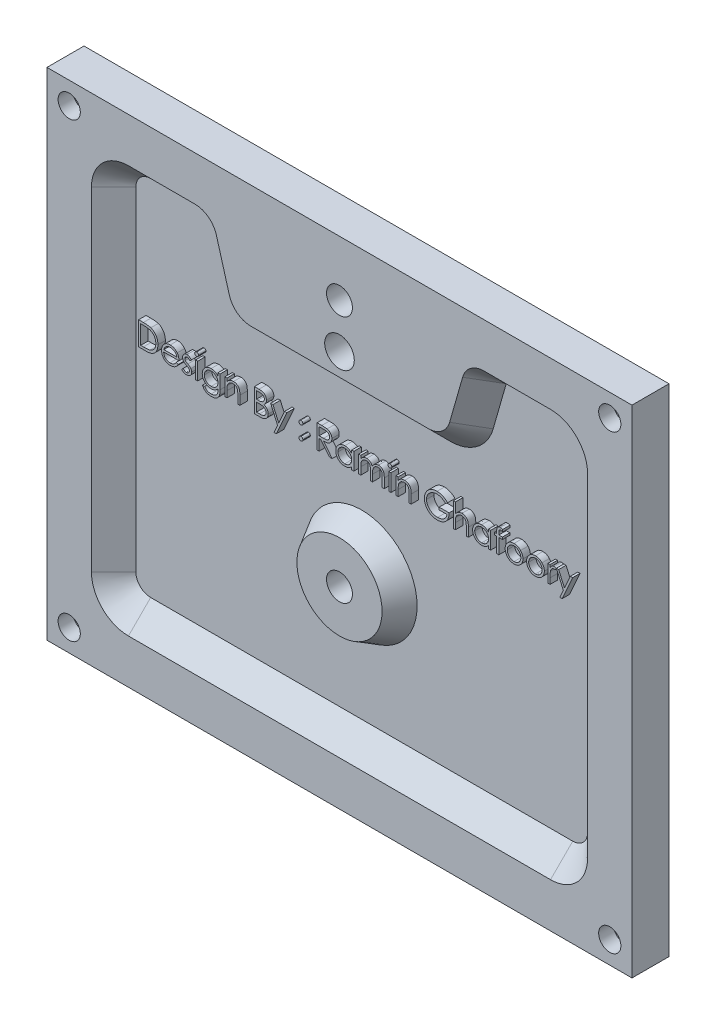
SolidWorks part; units mm, degrees
material "Ductile Iron"
ref_plane "Front" through (0, 0, 0) normal (0, 0, 1) x (1, 0, 0)
ref_plane "Top" through (0, 0, 0) normal (0, 1, 0) x (1, 0, 0)
ref_plane "Right" through (0, 0, 0) normal (1, 0, 0) x (0, 0, -1)
sketch "Sketch1" plane through (0, 0, 0) normal (0, 0, 1) x (1, 0, 0)
  line L1 (79, 67) -> (-79, 67)
  line L2 (79, 67) -> (79, -67)
  line L3 (79, -67) -> (-79, -67)
  line L4 (-79, 67) -> (-79, -67)
  point P4 (79, 0)
  point P6 (0, 67)
  dimension "D1" = 158
  dimension "D2" = 134
extrude "Boss-Extrude1" add sketch "Sketch1" along normal blind 10
sketch "Sketch2" plane through (0, 0, 10) normal (0, 0, 1) x (1, 0, 0)
  line L0 (-79, 67) -> (-79, -67) construction
  line L1 (57, 55) -> (39.0258, 55)
  line L2 (67, 45) -> (67, -45)
  line L3 (57, -55) -> (-57, -55)
  line L4 (-67, 45) -> (-67, -45)
  line L5 (79, 67) -> (-79, 67) construction
  line L6 (-79, -67) -> (79, -67) construction
  line L7 (79, -67) -> (79, 67) construction
  line L8 (33.2567, 50.6483) -> (29.7433, 38.3517)
  line L9 (23.9742, 34) -> (-23.9742, 34)
  line L10 (-29.7433, 38.3517) -> (-33.2567, 50.6483)
  line L11 (0, 0) -> (0, 34) construction
  line L12 (-39.0258, 55) -> (-57, 55)
  arc A0 (67, 45) -> (57, 55) centre (57, 45) ccw
  arc A1 (57, -55) -> (67, -45) centre (57, -45) ccw
  arc A2 (-57, -55) -> (-67, -45) centre (-57, -45) cw
  arc A3 (-67, 45) -> (-57, 55) centre (-57, 45) cw
  arc A4 (-29.7433, 38.3517) -> (-23.9742, 34) centre (-23.9742, 40) ccw
  arc A5 (23.9742, 34) -> (29.7433, 38.3517) centre (23.9742, 40) ccw
  arc A6 (-33.2567, 50.6483) -> (-39.0258, 55) centre (-39.0258, 49) ccw
  arc A7 (33.2567, 50.6483) -> (39.0258, 55) centre (39.0258, 49) cw
  point P22 (0, 34)
  point P32 (-28.5, 34)
  point P35 (28.5, 34)
  point P38 (-34.5, 55)
  dimension "D8" = 10
  dimension "D9" = 6
  dimension "D10" = 6
  dimension "D1" = 12
  dimension "D2" = 12
  dimension "D3" = 12
  dimension "D4" = 12
  dimension "D5" = 33
  dimension "D6" = 6
  dimension "D7" = 57
extrude "Cut-Extrude1" cut sketch "Sketch2" against normal blind 6
chamfer "Chamfer1" distance 6 angle 45 16 edges at (-64.0711, 52.0711, 4) (-67, 0, 4) (-48.0129, 55, 4) (-64.0711, -52.0711, 4) (-35.4126, 53.7901, 4) (0, -55, 4) (-31.5, 44.5, 4) (64.0711, -52.0711, 4) (-27.5874, 35.2099, 4) (67, 0, 4) (64.0711, 52.0711, 4) (48.0129, 55, 4) (35.4126, 53.7901, 4) (31.5, 44.5, 4) (27.5874, 35.2099, 4) (0, 34, 4)
sketch "Sketch3" plane through (0, 0, 10) normal (0, 0, 1) x (1, 0, 0)
  line L0 (57, 55) -> (39.0258, 55) construction
  circle A0 centre (0, -15) radius 11.5
  dimension "D2" = 23
  dimension "D1" = 70
extrude "Boss-Extrude2" add sketch "Sketch3" against normal up to next draft 30 draft outward yes
sketch "Sketch4" plane through (0, 0, 10) normal (0, 0, 1) x (1, 0, 0)
  circle A0 centre (0, -15) radius 3.5
  dimension "D1" = 7
extrude "Cut-Extrude2" cut sketch "Sketch4" against normal through all
sketch "Sketch5" plane through (0, 0, 10) normal (0, 0, 1) x (1, 0, 0)
  line L0 (79, 67) -> (-79, 67) construction
  line L1 (79, 67) -> (-79, 67) construction
  line L2 (-79, 67) -> (-79, -67) construction
  line L3 (-79, -67) -> (79, -67) construction
  line L4 (79, -67) -> (79, 67) construction
  circle A0 centre (0, 40) radius 4
  circle A1 centre (0, 52) radius 3.5
  circle A2 centre (-73, 61) radius 3
  circle A3 centre (73, 61) radius 3
  circle A4 centre (-73, -61) radius 3
  circle A5 centre (73, -61) radius 3
  point P4 (0, 67)
  dimension "D1" = 7
  dimension "D2" = 8
  dimension "D5" = 6
  dimension "D3" = 12
  dimension "D4" = 15
  dimension "D6" = 6
  dimension "D7" = 6
  dimension "D8" = 6
  dimension "D9" = 6
extrude "Cut-Extrude3" cut sketch "Sketch5" against normal through all
sketch "Sketch6" plane through (0, 0, 0) normal (0, 0, -1) x (-1, 0, 0)
  circle A0 centre (-73, 61) radius 4
  dimension "D1" = 8
extrude "Cut-Extrude4" cut sketch "Sketch6" against normal blind 6
pattern_linear "LPattern1" count 2 spacing 146 along (-1, 0, 0) count 2 spacing 122 along (0, -1, 0) of "Cut-Extrude4"
sketch "Sketch7" plane through (0, 0, 4) normal (0, 0, 1) x (1, 0, 0)
  line L0 (-61, 10) -> (61, 10) construction
  line L1 (-61, 45) -> (-61, -45) construction
  line L2 (61, -45) -> (61, 45) construction
  text T0 "Design By : Ramin Ghafoory"
  dimension "D1" = 10
extrude "Boss-Extrude3" add sketch "Sketch7" along normal blind 2
